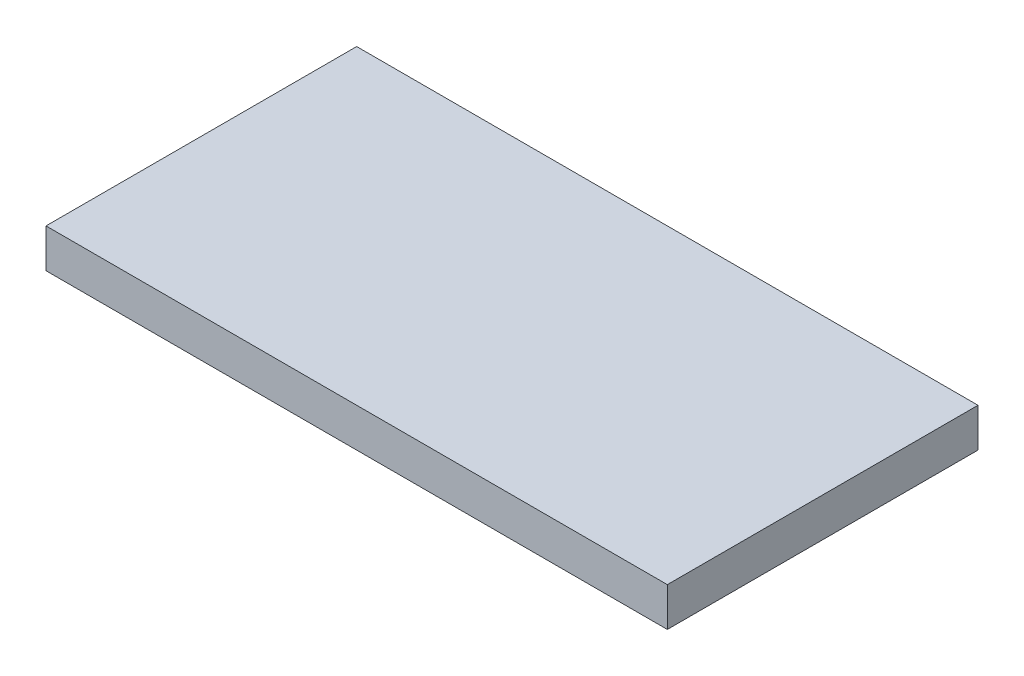
SolidWorks part; units mm, degrees
ref_plane "Front Plane" through (0, 0, 0) normal (0, 0, 1) x (1, 0, 0)
ref_plane "Top Plane" through (0, 0, 0) normal (0, 1, 0) x (1, 0, 0)
ref_plane "Right Plane" through (0, 0, 0) normal (1, 0, 0) x (0, 0, -1)
sketch "Sketch1" plane through (0, 0, 0) normal (0, 1, 0) x (1, 0, 0)
  line L1 (-160, 80) -> (160, 80)
  line L2 (-160, 80) -> (-160, -80)
  line L3 (-160, -80) -> (160, -80)
  line L4 (160, 80) -> (160, -80)
  line L5 (-160, 80) -> (160, -80) construction
  line L6 (-160, -80) -> (160, 80) construction
  point P0 (0, 0)
  dimension "D1" = 320
  dimension "D2" = 160
extrude "Boss-Extrude1" add sketch "Sketch1" along normal blind 20
